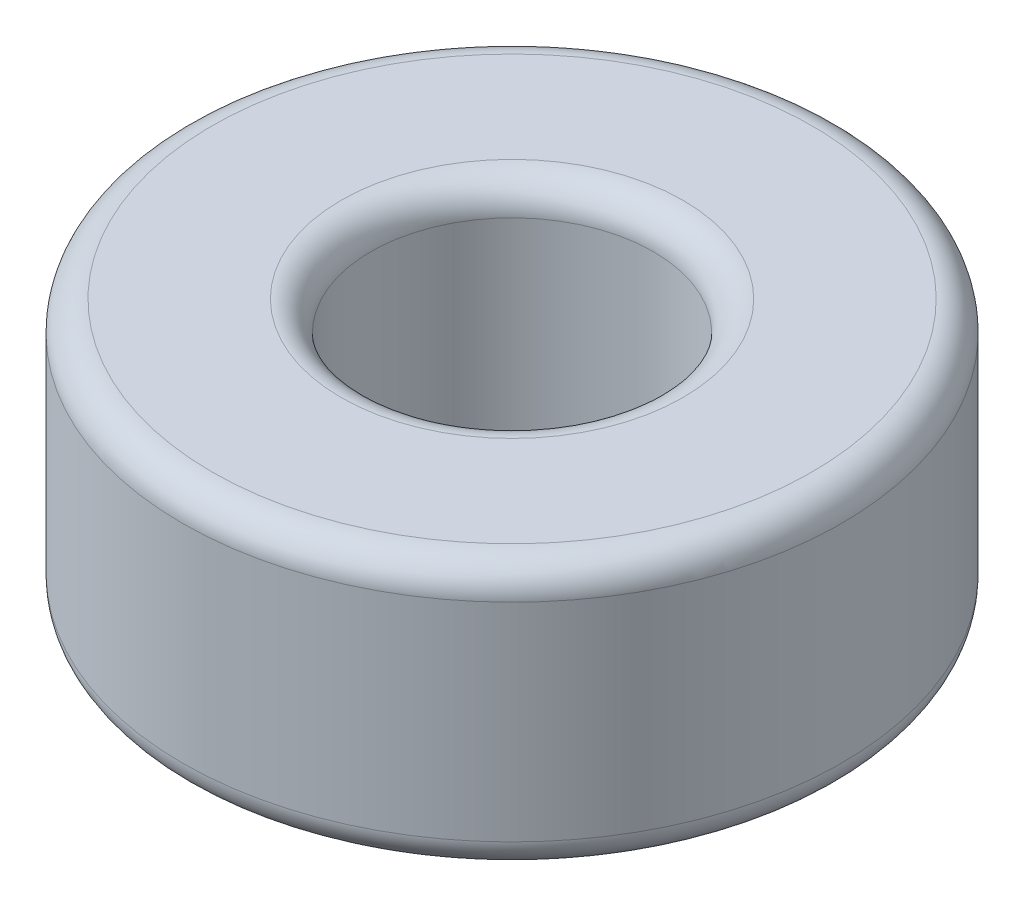
SolidWorks part; units mm, degrees
ref_plane "Front Plane" through (0, 0, 0) normal (0, 0, 1) x (1, 0, 0)
ref_plane "Top Plane" through (0, 0, 0) normal (0, 1, 0) x (1, 0, 0)
ref_plane "Right Plane" through (0, 0, 0) normal (1, 0, 0) x (0, 0, -1)
sketch "Sketch1" plane through (0, 0, 0) normal (0, 1, 0) x (1, 0, 0)
  circle A0 centre (0, 0) radius 4.7625
  circle A1 centre (0, 0) radius 11.1125
  dimension "D1" = 22.225
  dimension "D2" = 9.525
extrude "Boss-Extrude1" add sketch "Sketch1" along normal blind 4.5 and the other way blind 4.5
fillet "Fillet1" radius 1 2 edges at (0, -4.5, 4.7625) (0, 4.5, 4.7625)
fillet "Fillet2" radius 1 2 edges at (0, 4.5, 11.1125) (0, -4.5, 11.1125)
